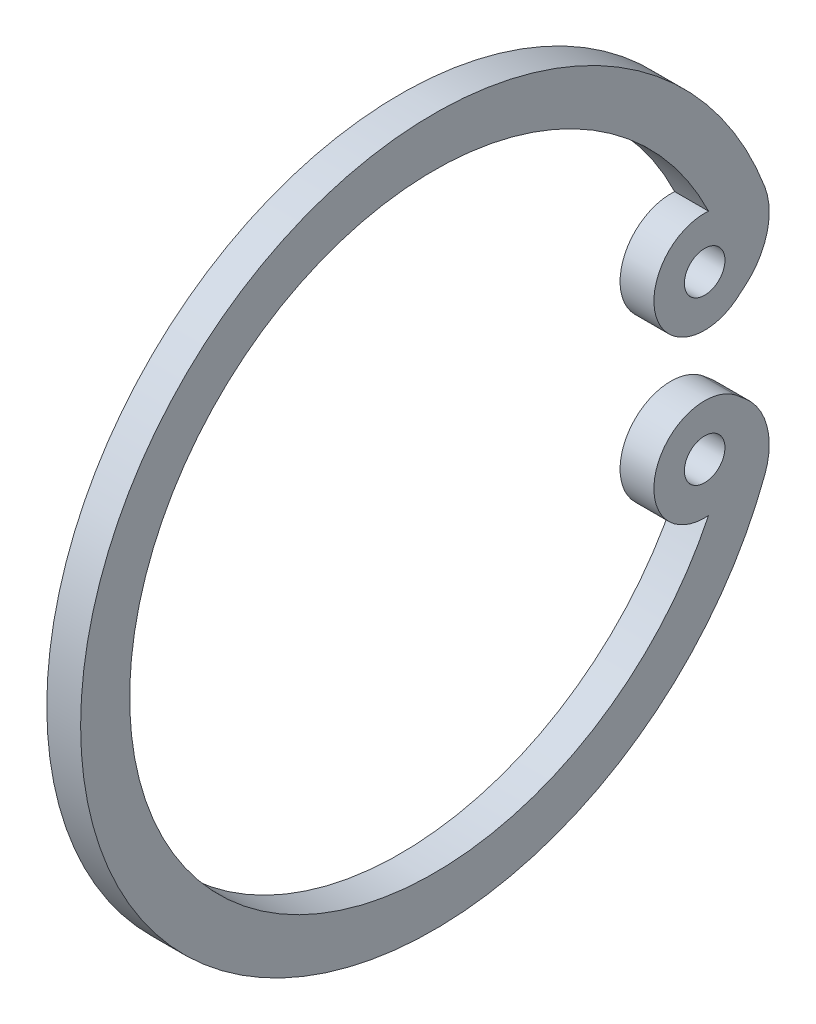
SolidWorks part; units mm, degrees
ref_plane "Front Plane" through (0, 0, 0) normal (0, 0, 1) x (1, 0, 0)
ref_plane "Top Plane" through (0, 0, 0) normal (0, 1, 0) x (1, 0, 0)
ref_plane "Right Plane" through (0, 0, 0) normal (1, 0, 0) x (0, 0, -1)
ref_plane "Plane1" through (19, 0, 0) normal (1, 0, 0) x (0, 0, -1)
sketch "Sketch1" plane through (19, 0, 0) normal (1, 0, 0) x (0, 0, -1)
  line L0 (-1.0829, 1.2142) -> (-0.8063, 1.4448)
  line L1 (-0.8063, -1.4451) -> (-1.0822, -1.2136)
  arc A0 (-1.8869, 3.8965) -> (-1.0829, 1.2142) centre (-2.0005, 2.4008) ccw
  arc A1 (-0.8063, 1.4448) -> (-0.2201, 3.6816) centre (-2.0918, 2.9769) ccw
  arc A2 (-0.2201, 3.6816) -> (-0.2201, -3.6818) centre (-9.9996, -0.0001) ccw
  arc A3 (-0.2201, -3.6818) -> (-0.8063, -1.4451) centre (-2.0918, -2.9772) ccw
  arc A4 (-1.0822, -1.2136) -> (-1.8869, -3.8967) centre (-2.0004, -2.4004) ccw
  arc A5 (-1.8869, -3.8967) -> (-1.8869, 3.8965) centre (-9.9996, -0.0001) cw
  circle A6 centre (-2, -2.4) radius 0.6
  circle A7 centre (-2, 2.4) radius 0.6
extrude "Boss-Extrude1" add sketch "Sketch1" against normal blind 1
scale "Scale1" scale about centroid uniform scaling yes scale factor 0.222222
